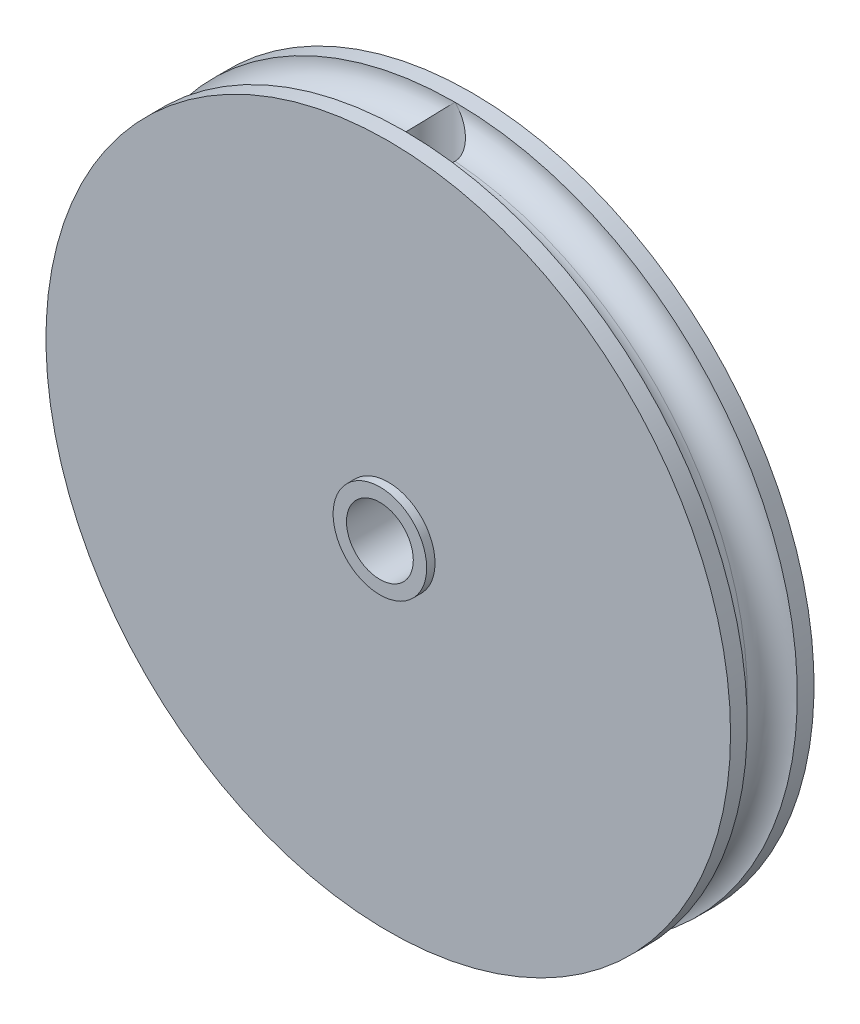
SolidWorks part; units mm, degrees
material "Alliage 6061"
ref_plane "Plan de face" through (0, 0, 0) normal (0, 0, 1) x (1, 0, 0)
ref_plane "Plan de dessus" through (0, 0, 0) normal (0, 1, 0) x (1, 0, 0)
ref_plane "Plan de droite" through (0, 0, 0) normal (1, 0, 0) x (0, 0, -1)
sketch "Esquisse1" plane through (0, 0, 0) normal (0, 0, 1) x (1, 0, 0)
  circle A0 centre (0, 0) radius 19
  dimension "D1" = 38
extrude "Boss.-Extru.1" add sketch "Esquisse1" along normal blind 3
sketch "Esquisse2" plane through (0, 0, 3) normal (0, 0, 1) x (1, 0, 0)
  circle A0 centre (0, 0) radius 20.5
  dimension "D1" = 41
extrude "Boss.-Extru.2" add sketch "Esquisse2" along normal blind 1
sketch "Esquisse3" plane through (0, 0, 0) normal (0, 0, -1) x (-1, 0, 0)
  circle A0 centre (0, 0) radius 20.5
  dimension "D1" = 41
extrude "Boss.-Extru.3" add sketch "Esquisse3" along normal blind 1
sketch "Esquisse4" plane through (0, 0, -1) normal (0, 0, -1) x (-1, 0, 0)
  circle A0 centre (0, 0) radius 2
  dimension "D1" = 4
extrude "Enlèv. mat.-Extru.1" cut sketch "Esquisse4" against normal through all
sketch "Esquisse5" plane through (0, 0, 0) normal (0, 1, 0) x (1, 0, 0)
  line L0 (20.5, 1) -> (-20.5, 1) construction
  circle A0 centre (0, -1.5) radius 1.5
  dimension "D1" = 3
  dimension "D2" = 2.5
extrude "Enlèv. mat.-Extru.4" cut sketch "Esquisse5" along normal through all
sketch "Esquisse6" plane through (0, 0, 4) normal (0, 0, 1) x (1, 0, 0)
  circle A0 centre (0, 0) radius 2.8
  circle A1 centre (0, 0) radius 2
  circle A2 centre (0, 0) radius 2 construction
  dimension "D1" = 5.6
extrude "Boss.-Extru.4" add sketch "Esquisse6" along normal blind 0.5
sketch "Esquisse7" plane through (0, 0, -1) normal (0, 0, -1) x (-1, 0, 0)
  circle A0 centre (0, 0) radius 2 construction
  circle A1 centre (0, 0) radius 2.8
  circle A2 centre (0, 0) radius 2.8
  circle A3 centre (0, 0) radius 2
  dimension "D1" = 0
extrude "Boss.-Extru.5" add sketch "Esquisse7" along normal blind 0.5
fillet "Congé1" [suppressed] radius 0.5
fillet "Congé2" radius 1.5 2 edges at (-19, 0, 0) (19, 0, 3)
